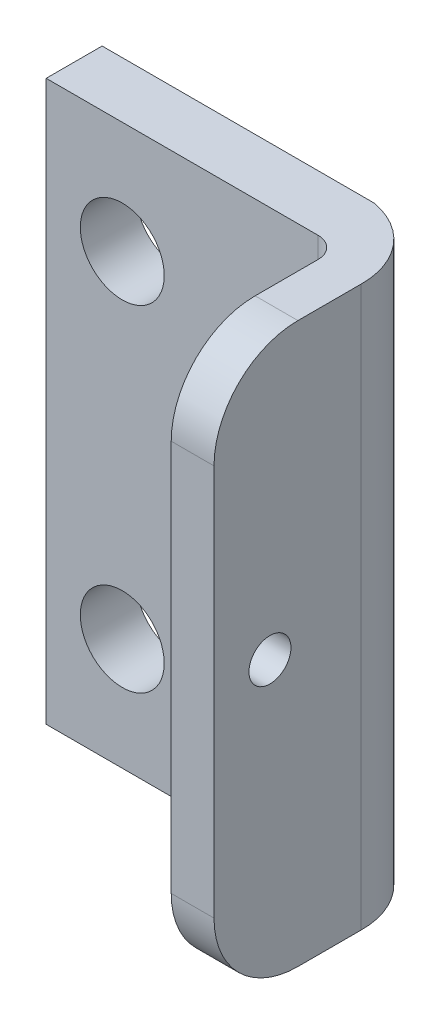
SolidWorks part; units mm, degrees
ref_plane "Front Plane" through (0, 0, 0) normal (0, 0, 1) x (1, 0, 0)
ref_plane "Top Plane" through (0, 0, 0) normal (0, 1, 0) x (1, 0, 0)
ref_plane "Right Plane" through (0, 0, 0) normal (1, 0, 0) x (0, 0, -1)
sketch "Sketch1" plane through (0, 0, 0) normal (0, 0, 1) x (1, 0, 0)
  line L1 (0, 0) -> (9.72, 0)
  line L2 (0, 0) -> (0, 20)
  line L3 (0, 20) -> (9.72, 20)
  line L4 (9.72, 0) -> (9.72, 20)
  line L5 (4.86, 20) -> (4.86, 0) construction
  line L6 (0, 10) -> (9.72, 10) construction
  circle A0 centre (2.72, 16) radius 1.5
  circle A1 centre (2.72, 4) radius 1.5
  point P380 (4.86, 10)
  dimension "D2" = 3
  dimension "D3" = 3
  dimension "D1" = 20
  dimension "D4" = 4
  dimension "D5" = 4
  dimension "D6" = 2.72
  dimension "D7" = 7
extrude "Boss-Extrude1" add sketch "Sketch1" along normal blind 2
sketch "Sketch2" plane through (0, 0, 0) normal (0, -1, 0) x (1, 0, 0)
  line L0 (9.72, 2) -> (9.72, 0)
  line L1 (11.9997, 2.75) -> (10.47, 2.75)
  line L2 (0, 2) -> (9.72, 2) construction
  arc A0 (9.72, 0) -> (11.9997, 2.75) centre (9.25, 2.7095) ccw
  arc A2 (9.72, 2) -> (10.47, 2.75) centre (9.72, 2.75) ccw
  dimension "D1" = 5.5
  dimension "D3" = 1.5
  dimension "D2" = 0.47
  dimension "D4" = 0.75
  dimension "D5" = 0.75
extrude "Boss-Extrude2" add sketch "Sketch2" against normal blind 20
ref_plane "Plane1" through (12, 0, 0) normal (1, 0, 0) x (0, 0, -1)
sketch "Sketch3" plane through (12, 0, 0) normal (1, 0, 0) x (0, 0, -1)
  line L0 (-2.75, 20) -> (-5, 20)
  line L1 (-8, 17) -> (-8, 3)
  line L2 (-5, 0) -> (-2.75, 0)
  line L3 (-2.75, 20) -> (-2.75, 0)
  line L4 (0, 0) -> (0, 20) construction
  arc A0 (-8, 3) -> (-5, 0) centre (-5, 3) ccw
  arc A1 (-5, 20) -> (-8, 17) centre (-5, 17) ccw
  circle A2 centre (-6, 10) radius 0.75
  dimension "D2" = 3
  dimension "D3" = 1.5
  dimension "D1" = 8
  dimension "D4" = 2
  dimension "D5" = 10
extrude "Boss-Extrude3" add sketch "Sketch3" against normal up to vertex (1.53 mm away) up to point (10.47, 0, 2.75)
